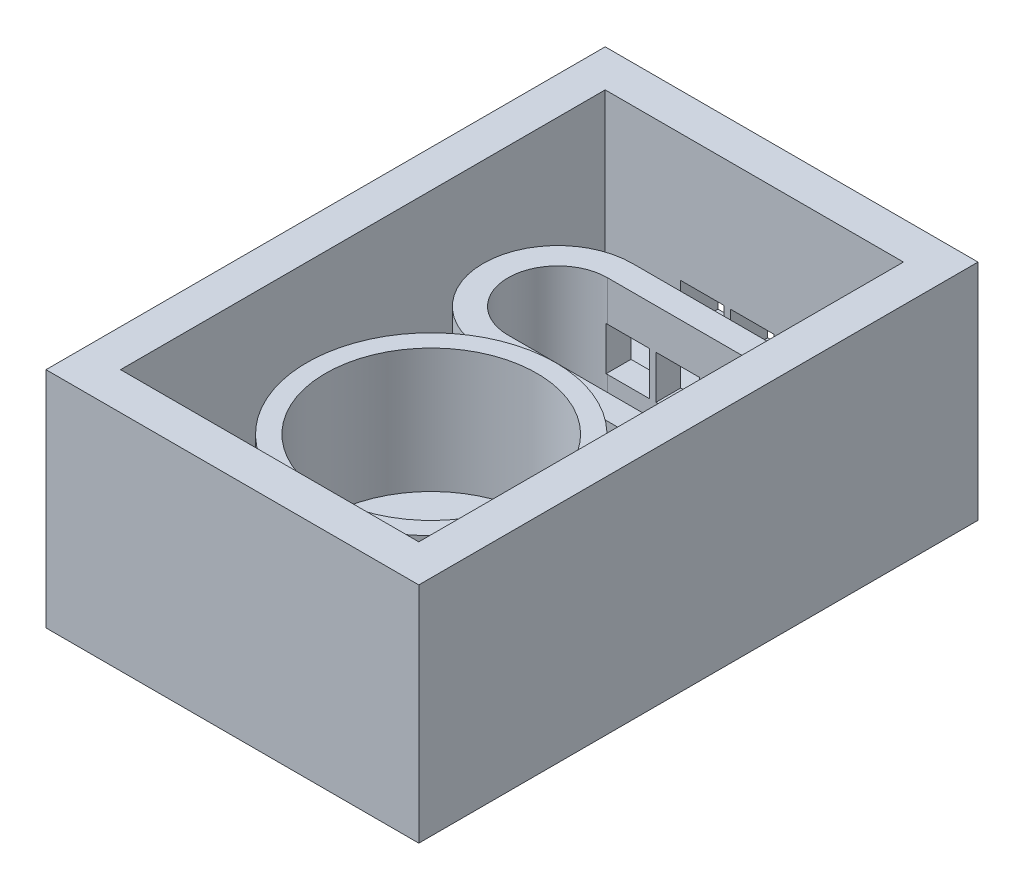
SolidWorks part; units mm, degrees
ref_plane "Front Plane" through (0, 0, 0) normal (0, 0, 1) x (1, 0, 0)
ref_plane "Top Plane" through (0, 0, 0) normal (0, 1, 0) x (1, 0, 0)
ref_plane "Right Plane" through (0, 0, 0) normal (1, 0, 0) x (0, 0, -1)
sketch "Sketch1" plane through (0, 0, 0) normal (0, 1, 0) x (1, 0, 0)
  line L0 (0, 0) -> (0, -32.988) construction
  line L9 (15, -16) -> (-15, -16)
  line L10 (15, -16) -> (15, 29)
  line L11 (15, 29) -> (-15, 29)
  line L12 (-15, -16) -> (-15, 29)
  line L13 (15, -16) -> (-15, 29) construction
  line L14 (15, 29) -> (-15, -16) construction
  line L16 (-12, 26) -> (12, 26)
  line L17 (-12, 26) -> (-12, -13)
  line L18 (-12, -13) -> (12, -13)
  line L19 (12, 26) -> (12, -13)
  line L20 (-12, 26) -> (12, -13) construction
  line L21 (-12, -13) -> (12, 26) construction
  circle A0 centre (0, 0) radius 8.5
  circle A1 centre (0, 0) radius 10
  point P4 (0, 0)
  point P10 (0, 6.5)
  point P15 (12, -11.106)
  dimension "D1" = 17
  dimension "D2" = 20
  dimension "D3" = 45
  dimension "D4" = 30
  dimension "D5" = 16
  dimension "D6" = 3
  dimension "D7" = 3
extrude "Boss-Extrude4" add sketch "Sketch1" along normal blind 10 contours L12 L9 L10 L11 L16 L19 L18 L17 | A1 A0 region at (0, 0, 15.4592) region at (-9.7172, 0, 0)
extrude "Boss-Extrude5" add sketch "Sketch1<5>" along normal blind 15 contours L12 L9 L10 L11 L16 L19 L18 L17 region at (0, 0, 15.4592)
sketch "Sketch1<5>" plane through (0, 0, 0) normal (0, 1, 0) x (1, 0, 0) same geometry as "Sketch1"
sketch "Sketch3" plane through (0, 0, 0) normal (0, -1, 0) x (1, 0, 0)
  line L1 (-15, 16) -> (15, 16)
  line L2 (-15, 16) -> (-15, -29)
  line L3 (-15, -29) -> (15, -29)
  line L4 (15, 16) -> (15, -29)
extrude "Boss-Extrude6" add sketch "Sketch3" along normal blind 3
sketch "Sketch4" plane through (0, 0, 0) normal (0, 1, 0) x (1, 0, 0)
  line L0 (-5.816, 16) -> (5.5762, 16) construction
  line L1 (-5.816, 20) -> (5.5762, 20)
  line L2 (-5.816, 12) -> (5.5762, 12)
  line L3 (-5.816, 16) -> (5.5762, 16) construction
  line L4 (-5.816, 22) -> (5.5762, 22)
  line L5 (-5.816, 10) -> (5.5762, 10)
  arc A0 (-5.816, 20) -> (-5.816, 12) centre (-5.816, 16) ccw
  arc A1 (5.5762, 12) -> (5.5762, 20) centre (5.5762, 16) ccw
  arc A3 (-5.816, 22) -> (-5.816, 10) centre (-5.816, 16) ccw
  arc A4 (5.5762, 10) -> (5.5762, 22) centre (5.5762, 16) ccw
  point P2 (-0.1199, 16)
  point P11 (-0.1199, 16)
  dimension "D2" = 2
  dimension "D1" = 10
  dimension "D3" = 8
extrude "Boss-Extrude9" add sketch "Sketch4" along normal blind 8 separate body
sketch "Sketch6" plane through (0, 0, -26) normal (0, 0, 1) x (1, 0, 0)
  line L1 (2.0762, 4.7579) -> (5.5762, 4.7579)
  line L2 (2.0762, 4.7579) -> (2.0762, 1.2579)
  line L3 (2.0762, 1.2579) -> (5.5762, 1.2579)
  line L4 (5.5762, 4.7579) -> (5.5762, 1.2579)
  line L5 (1.5762, 4.7579) -> (1.5762, 1.2579)
  line L6 (-1.9238, 4.7579) -> (-1.9238, 1.2579)
  line L7 (-1.9238, 4.7579) -> (1.5762, 4.7579)
  line L8 (-1.9238, 1.2579) -> (1.5762, 1.2579)
  line L9 (-2.4238, 4.7579) -> (-2.4238, 1.2579)
  line L10 (-5.9238, 4.7579) -> (-5.9238, 1.2579)
  line L11 (-5.9238, 4.7579) -> (-2.4238, 4.7579)
  line L12 (-5.9238, 1.2579) -> (-2.4238, 1.2579)
  line L13 (5.5762, 8) -> (5.5762, 0) construction
  dimension "D1" = 3.5
  dimension "D2" = 3.5
  dimension "D4" = 3
extrude "Cut-Extrude2" cut sketch "Sketch6" against normal blind 8 and the other way blind 11
